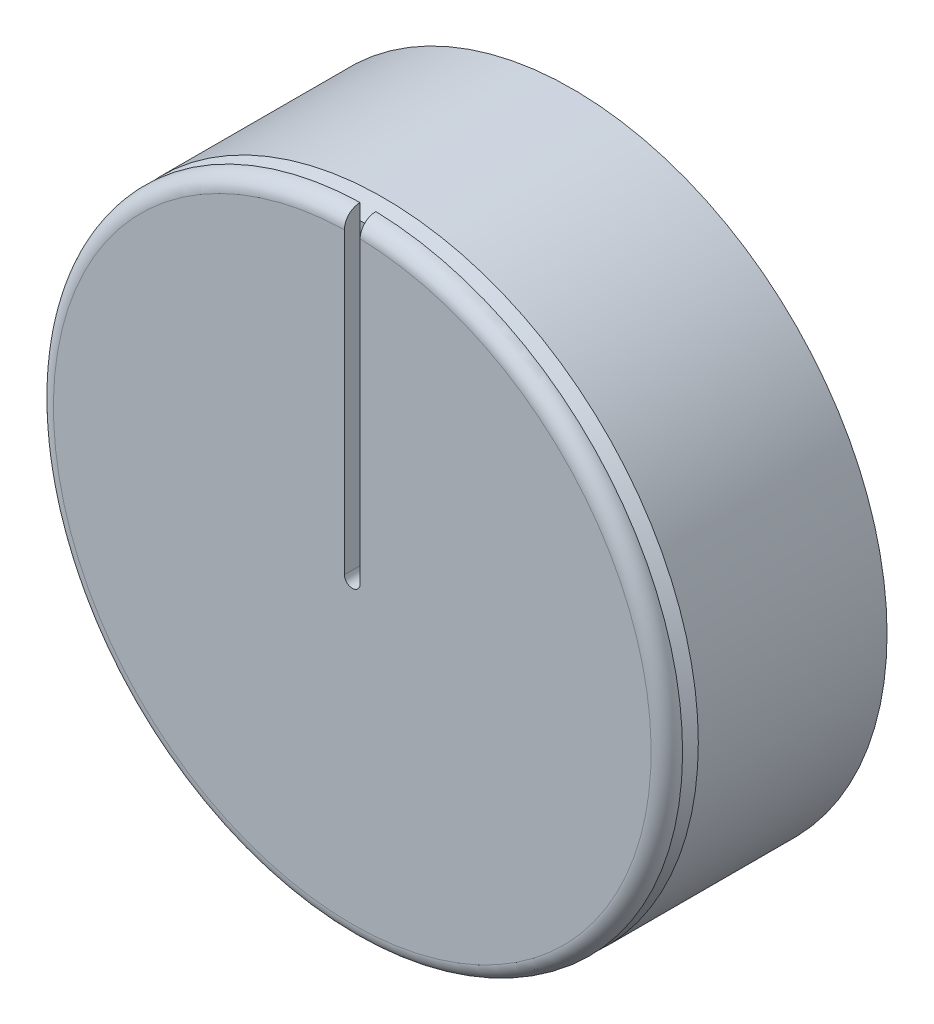
SolidWorks part; units mm, degrees
ref_plane "Front Plane" through (0, 0, 0) normal (0, 0, 1) x (1, 0, 0)
ref_plane "Top Plane" through (0, 0, 0) normal (0, 1, 0) x (1, 0, 0)
ref_plane "Right Plane" through (0, 0, 0) normal (1, 0, 0) x (0, 0, -1)
sketch "Sketch1" plane through (0, 0, 0) normal (0, 0, 1) x (1, 0, 0)
  circle A0 centre (51.182, -61.9744) radius 20
  dimension "D1" = 40
extrude "Boss-Extrude1" add sketch "Sketch1" along normal blind 14 from offset 1
fillet "Fillet2" radius 1 1 edges at (71.182, -61.9744, 15)
sketch "Sketch2" plane through (0, 0, 15) normal (0, 0, 1) x (1, 0, 0)
  line L0 (51.182, -42.9744) -> (51.182, -80.9744) construction
  circle A0 centre (51.182, -61.9744) radius 19 construction
ref_plane "Plane1" through (51.182, 0, 0) normal (1, 0, 0) x (0, 0, -1)
sketch "Sketch3" plane through (0, 0, 15) normal (0, 0, 1) x (1, 0, 0)
  line L0 (51.182, -61.9744) -> (51.182, -41.9744) construction
  line L1 (50.682, -61.9744) -> (50.682, -41.9744)
  line L2 (51.682, -61.9744) -> (51.682, -41.9744)
  circle A0 centre (51.182, -61.9744) radius 20 construction
  arc A1 (50.682, -61.9744) -> (51.682, -61.9744) centre (51.182, -61.9744) ccw
  arc A2 (51.682, -41.9744) -> (50.682, -41.9744) centre (51.182, -41.9744) ccw
  point P5 (51.182, -51.9744)
  dimension "D1" = 1
extrude "Cut-Extrude1" cut sketch "Sketch3" against normal blind 1
sketch "Sketch4" plane through (0, 0, 15) normal (0, 0, 1) x (1, 0, 0)
  circle A0 centre (51.182, -61.9744) radius 20
  circle A1 centre (51.182, -61.9744) radius 19
  arc A2 (50.682, -41.9806) -> (51.682, -41.9806) centre (51.182, -61.9744) ccw construction
  dimension "D1" = 1
extrude "Cut-Extrude2" cut sketch "Sketch4" against normal blind 1 from surface contours A1 | A0 starting at face at (51.182, -52.1009, 14)
chamfer "Chamfer1" distance 1 angle 45 1 edges at (70.182, -61.9744, 13)
sketch "Sketch5" plane through (0, 0, 1) normal (0, 0, -1) x (-1, 0, 0)
  line L0 (-51.182, -42.9744) -> (-51.182, -80.9744) construction
  circle A0 centre (-51.182, -61.9744) radius 3.025
  dimension "D1" = 6.05
extrude "Cut-Extrude3" cut sketch "Sketch5" against normal blind 10.5
sketch "Sketch6" plane through (0, 0, 1) normal (0, 0, -1) x (-1, 0, 0)
  line L0 (-51.182, -42.9744) -> (-51.182, -80.9744) construction
  circle A0 centre (-51.182, -61.9744) radius 10
  dimension "D1" = 20
extrude "Cut-Extrude4" cut sketch "Sketch6" against normal blind 5
